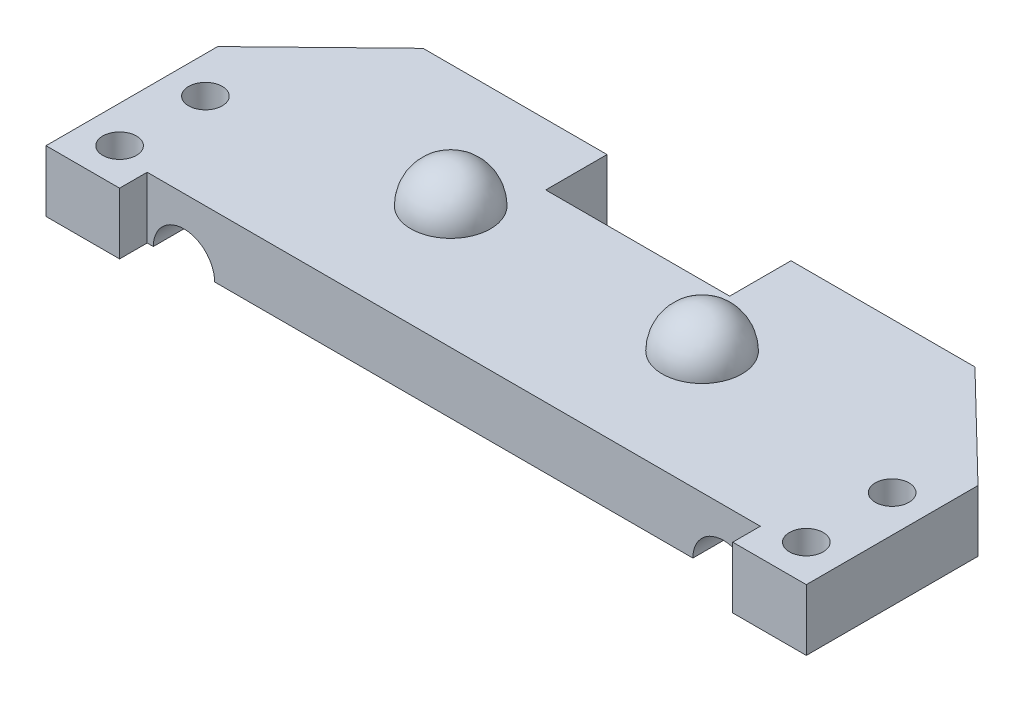
SolidWorks part; units mm, degrees
ref_plane "Front" through (0, 0, 0) normal (0, 0, 1) x (1, 0, 0)
ref_plane "Top" through (0, 0, 0) normal (0, 1, 0) x (1, 0, 0)
ref_plane "Right" through (0, 0, 0) normal (1, 0, 0) x (0, 0, -1)
sketch "Sketch1" plane through (0, 0, 0) normal (0, 1, 0) x (1, 0, 0)
  line L1 (0, 0) -> (45, 0)
  line L2 (0, 0) -> (0, 20)
  line L3 (0, 20) -> (45, 20)
  line L4 (45, 0) -> (45, 20)
  dimension "D1" = 20
  dimension "D2" = 45
extrude "bracketBase" add sketch "Sketch1" along normal blind 5
sketch "Sketch2" plane through (0, 5, 0) normal (0, 1, 0) x (1, 0, 0)
  line L0 (0, 20) -> (0, 0) construction
  line L3 (45, 20) -> (0, 20) construction
  line L4 (12.25, 13.25) -> (12.25, 6.75)
  arc A0 (12.25, 13.25) -> (12.25, 6.75) centre (12.25, 10) ccw
  dimension "D3" = 6.5
  dimension "D1" = 12.25
  dimension "D2" = 10
revolve "ballPoint1" add sketch "Sketch2" angle 360 about L4
ref_plane "referencePlane1" through (22.5, 0, 0) normal (-1, 0, 0) x (0, 0, 1)
mirror "Mirror1" about plane through (22.5, 0, 0) normal (-1, 0, 0) of "ballPoint1"
sketch "Sketch3" plane through (0, 0, 0) normal (0, -1, 0) x (1, 0, 0)
  line L0 (22.5, 0) -> (22.5, -20) construction
  line L1 (0, 0) -> (45, 0) construction
  line L2 (45, -20) -> (0, -20) construction
  line L3 (45, 0) -> (45, -20) construction
  line L4 (53.5, -11.75) -> (47.5, -11.75) construction
  line L5 (53.5, -11.75) -> (53.5, 2.25) construction
  line L6 (53.5, 2.25) -> (47.5, 2.25) construction
  line L7 (47.5, -11.75) -> (47.5, 2.25) construction
  line L8 (45, -20) -> (53.5, -11.75)
  line L9 (53.5, -11.75) -> (53.5, 2.25)
  line L10 (53.5, 2.25) -> (47.5, 2.25)
  line L11 (47.5, 2.25) -> (47.5, 0)
  line L12 (47.5, 0) -> (45, 0)
  line L13 (45, 0) -> (45, -20)
  line L14 (-2.5, 0) -> (0, 0)
  line L15 (-2.5, 2.25) -> (-2.5, 0)
  line L16 (-8.5, 2.25) -> (-2.5, 2.25)
  line L17 (-8.5, -11.75) -> (-8.5, 2.25)
  line L18 (0, -20) -> (-8.5, -11.75)
  line L19 (0, 0) -> (0, -20)
  circle A0 centre (50.5, -0.75) radius 1.375
  circle A1 centre (50.5, -7.75) radius 1.375
  circle A2 centre (-5.5, -0.75) radius 1.375
  circle A3 centre (-5.5, -7.75) radius 1.375
  point P19 (50.5, 2.25)
  point P22 (50.5, -11.75)
  dimension "D5" = 2.75
  dimension "D1" = 14
  dimension "D2" = 6
  dimension "D3" = 2.5
  dimension "D4" = 8.25
  dimension "D6" = 3
  dimension "D7" = 4
extrude "mountingTabs" add sketch "Sketch3" against normal up to surface (5 mm away) up to face at (32.75, 5, -13.25)
sketch "Sketch4" plane through (0, 0, 0) normal (0, -1, 0) x (1, 0, 0)
  line L0 (45, -20) -> (0, -20) construction
  line L1 (30, -20) -> (15, -20)
  line L2 (30, -20) -> (30, -15)
  line L3 (30, -15) -> (15, -15)
  line L4 (15, -20) -> (15, -15)
  point P4 (22.5, -20)
  point P7 (22.5, -20)
  dimension "D1" = 5
  dimension "D2" = 15
extrude "headerSlot" cut sketch "Sketch4" against normal blind 13.625
sketch "Sketch6" plane through (0, 0, 0) normal (0, 0, 1) x (1, 0, 0)
  line L0 (22.5, 0) -> (22.5, 5) construction
  line L1 (-2.5, 0) -> (47.5, 0) construction
  line L2 (-2.5, 5) -> (47.5, 5) construction
  circle A0 centre (44.5, 0) radius 2.5
  circle A1 centre (0.5, 0) radius 2.5
  dimension "D1" = 5
  dimension "D2" = 9
extrude "Cut-Extrude1" cut sketch "Sketch6" against normal through all both and the other way through all
